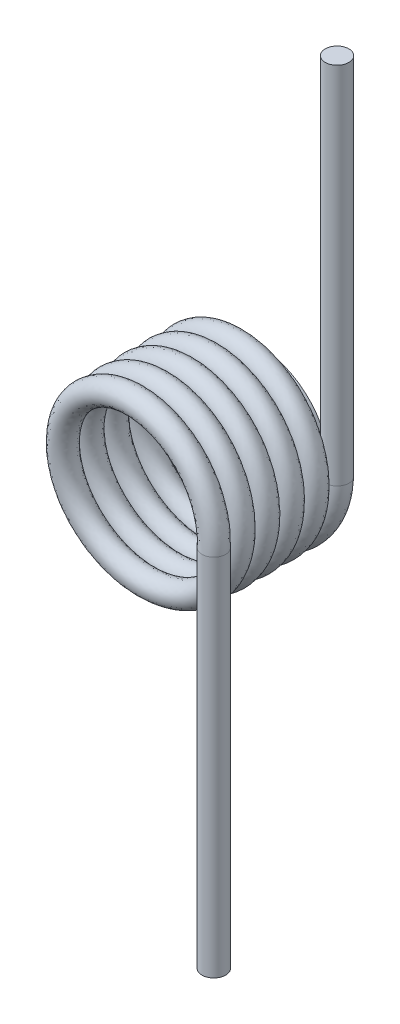
SolidWorks part; units mm, degrees
ref_plane "Спереди" through (0, 0, 0) normal (0, 0, 1) x (1, 0, 0)
ref_plane "Сверху" through (0, 0, 0) normal (0, 1, 0) x (1, 0, 0)
ref_plane "Справа" through (0, 0, 0) normal (1, 0, 0) x (0, 0, -1)
sketch "Эскиз1" plane through (0, 0, 0) normal (0, 0, 1) x (1, 0, 0)
  circle A0 centre (0, 0) radius 2.35
curve "Спираль1" pitch 0.71 height 3.55 radius 2.35 left hand yes centre (0, 0, 0) axis (0, 0, 1) start towards (1, 0, 0)
sketch "Эскиз6" plane through (0, 0, 0) normal (0, 1, 0) x (1, 0, 0)
  circle A0 centre (2.35, 0) radius 0.34
  spline S0 degree 3 poles (2.35, 0) (2.35, -0.0147) (2.2276, -0.0444) (1.705, -0.0887) (0.9227, -0.1331) (0, -0.1775) (-0.9227, -0.2219) (-1.705, -0.2662) (-2.2276, -0.3106) (-2.4112, -0.355) (-2.2276, -0.3994) (-1.705, -0.4437) (-0.9227, -0.4881) (0, -0.5325) (0.9227, -0.5769) (1.705, -0.6212) (2.2276, -0.6656) (2.4112, -0.71) (2.2276, -0.7544) (1.705, -0.7987) (0.9227, -0.8431) (0, -0.8875) (-0.9227, -0.9319) (-1.705, -0.9763) (-2.2276, -1.0206) (-2.4112, -1.065) (-2.2276, -1.1094) (-1.705, -1.1538) (-0.9227, -1.1981) (0, -1.2425) (0.9227, -1.2869) (1.705, -1.3313) (2.2276, -1.3756) (2.4112, -1.42) (2.2276, -1.4644) (1.705, -1.5087) (0.9227, -1.5531) (0, -1.5975) (-0.9227, -1.6419) (-1.705, -1.6862) (-2.2276, -1.7306) (-2.4112, -1.775) (-2.2276, -1.8194) (-1.705, -1.8637) (-0.9227, -1.9081) (0, -1.9525) (0.9227, -1.9969) (1.705, -2.0412) (2.2276, -2.0856) (2.4112, -2.13) (2.2276, -2.1744) (1.705, -2.2187) (0.9227, -2.2631) (0, -2.3075) (-0.9227, -2.3519) (-1.705, -2.3962) (-2.2276, -2.4406) (-2.4112, -2.485) (-2.2276, -2.5294) (-1.705, -2.5738) (-0.9227, -2.6181) (0, -2.6625) (0.9227, -2.7069) (1.705, -2.7513) (2.2276, -2.7956) (2.4112, -2.84) (2.2276, -2.8844) (1.705, -2.9288) (0.9227, -2.9731) (0, -3.0175) (-0.9227, -3.0619) (-1.705, -3.1063) (-2.2276, -3.1506) (-2.4112, -3.195) (-2.2276, -3.2394) (-1.705, -3.2838) (-0.9227, -3.3281) (0, -3.3725) (0.9227, -3.4169) (1.705, -3.4613) (2.2276, -3.5056) (2.35, -3.5353) (2.35, -3.55) knots 0 0 0 0 0.0125 0.025 0.0375 0.05 0.0625 0.075 0.0875 0.1 0.1125 0.125 0.1375 0.15 0.1625 0.175 0.1875 0.2 0.2125 0.225 0.2375 0.25 0.2625 0.275 0.2875 0.3 0.3125 0.325 0.3375 0.35 0.3625 0.375 0.3875 0.4 0.4125 0.425 0.4375 0.45 0.4625 0.475 0.4875 0.5 0.5125 0.525 0.5375 0.55 0.5625 0.575 0.5875 0.6 0.6125 0.625 0.6375 0.65 0.6625 0.675 0.6875 0.7 0.7125 0.725 0.7375 0.75 0.7625 0.775 0.7875 0.8 0.8125 0.825 0.8375 0.85 0.8625 0.875 0.8875 0.9 0.9125 0.925 0.9375 0.95 0.9625 0.975 0.9875 1 1 1 1 construction
sweep "По траектории9" add profiles "Эскиз6" path "Спираль1"
sketch "Эскиз7" plane through (0, 0, 0) normal (0, -1, 0) x (1, 0, 0)
  circle A0 centre (2.35, 3.55) radius 0.34
extrude "Вытянуть1" add sketch "Эскиз7" along normal blind 10.5
sketch "Эскиз8" plane through (0, 0, 0) normal (0, 1, 0) x (1, 0, 0)
  circle A0 centre (2.35, 0) radius 0.34
extrude "Вытянуть2" add sketch "Эскиз8" along normal blind 10.5
sketch "Эскиз9" plane through (0, 0, 0) normal (0, 0, 1) x (1, 0, 0)
  circle A0 centre (0, 0) radius 2
sketch "Эскиз12" plane through (0, 0, 0) normal (0, 1, 0) x (1, 0, 0)
  line L2 (-2.0693, 0.0721) -> (-1.9307, 0.0721)
  line L3 (-2.0693, 0.0721) -> (-2.0693, -0.0721)
  line L4 (-2.0693, -0.0721) -> (-1.9307, -0.0721)
  line L5 (-1.9307, 0.0721) -> (-1.9307, -0.0721)
  line L6 (-2.0693, 0.0721) -> (-1.9307, -0.0721) construction
  line L7 (-2.0693, -0.0721) -> (-1.9307, 0.0721) construction
sweep "По траектории12" add profiles "Эскиз12" path "Эскиз9"
